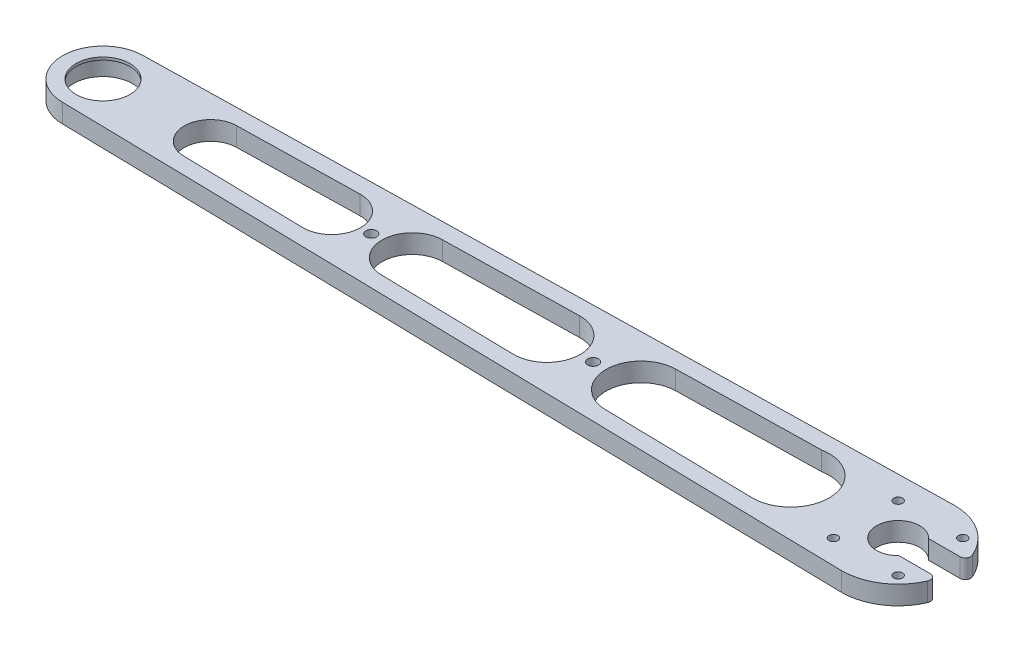
SolidWorks part; units mm, degrees
material "1060 Alloy"
ref_plane "Front Plane" through (0, 0, 0) normal (0, 0, 1) x (1, 0, 0)
ref_plane "Top Plane" through (0, 0, 0) normal (0, 1, 0) x (1, 0, 0)
ref_plane "Right Plane" through (0, 0, 0) normal (1, 0, 0) x (0, 0, -1)
sketch "Sketch1" plane through (0, 0, 0) normal (0, 1, 0) x (1, 0, 0)
  line L0 (-44.2539, 0) -> (44.2539, 0) construction
  line L1 (247.4804, -21) -> (-48.0196, -15)
  line L2 (-48.0196, 15) -> (247.4804, 21)
  line L3 (253.2898, 5.5) -> (264.9375, 5.5)
  line L4 (253.2898, -5.5) -> (264.9375, -5.5)
  arc A0 (-48.0196, 15) -> (-48.0196, -15) centre (-48.0196, 0) ccw
  arc A1 (246.6279, -20.9827) -> (266.775, -8.2895) centre (247.4804, 0) ccw
  arc A2 (253.2898, 5.5) -> (253.2898, -5.5) centre (247.4804, 0) ccw
  arc A3 (266.775, 8.2895) -> (246.6279, 20.9827) centre (247.4804, 0) ccw
  arc A4 (264.9375, 5.5) -> (266.775, 8.2895) centre (264.9375, 7.5) ccw
  arc A5 (264.9375, -5.5) -> (266.775, -8.2895) centre (264.9375, -7.5) cw
  circle A6 centre (-48.0196, 0) radius 10
  point P16 (267.7473, 5.5)
  dimension "D1" = 42
  dimension "D2" = 30
  dimension "D4" = 16
  dimension "D7" = 2
  dimension "D3" = 295.5
  dimension "D5" = 11
  dimension "D6" = 5.5
extrude "Boss-Extrude1" add sketch "Sketch1" along normal blind 7 contours A5 L4 A2 L3 A4 A3 L2 A0 L1 A1 A6 region at (111.8502, 0, 0)
ref_axis "Axis1" through (247.4804, 52.1339, 0) along (0, -1, 0)
ref_plane "Plane1" through (123.7402, 0, 123.7402) normal (0.7071, 0, 0.7071) x (0, -1, 0)
hole_wizard "Tap Drill for M4 Tap1" positions "Sketch2" profile "Sketch3" hole size "M4" standard "ISO"
sketch "Sketch2" plane through (0, 7, 0) normal (0, 1, 0) x (1, 0, 0)
  line L0 (96.347, -151.1333) -> (151.1333, -96.347) construction
  point P0 (259.5012, 12.0208)
  dimension "D1" = 17
sketch "Sketch3" plane through (259.5012, 7, -12.0208) normal (1, 0, 0) x (0, 0, 1)
  line L0 (0, 0) -> (0, 8.9914)
  line L1 (0, 8.9914) -> (1.65, 8)
  line L2 (1.65, 8) -> (1.65, 0)
  line L5 (1.65, 0) -> (0, 0)
  line L10 (0, 8.9914) -> (-1.65, 8) construction
  line L11 (0, -6.35) -> (0, 107.95) construction
  dimension "Hole Dia." = 3.3
  dimension "Hole Depth" = 8
  dimension "Drill Angle" = 118
pattern_circular "CirPattern1" count 4 over 360 about axis through (247.4804, 52.1339, 0) along (0, -1, 0) of "Tap Drill for M4 Tap1"
sketch "Sketch4" plane through (0, 0, 0) normal (0, 1, 0) x (1, 0, 0)
  circle A0 centre (-48.0196, 0) radius 11
extrude "Cut-Extrude2" cut sketch "Sketch4" along normal blind 6
hole_wizard "M4 Tapped Hole1" positions "Sketch5" profile "Sketch6" tap size "M4" standard "ISO"
sketch "Sketch5" plane through (0, 0, 0) normal (0, -1, 0) x (-1, 0, 0)
  line L0 (-44.2539, 0) -> (44.2539, 0) construction
  circle A0 centre (48.0196, 0) radius 11 construction
  point P0 (33.0196, -10)
  point P2 (33.0196, 10)
  dimension "D1" = 15
  dimension "D2" = 0
  dimension "D3" = 10
  dimension "D4" = 10
sketch "Sketch6" plane through (-33.0196, 0, 10) normal (1, 0, 0) x (0, 0, -1)
  line L0 (0, 0) -> (0, 5.9914)
  line L1 (0, 5.9914) -> (1.65, 5)
  line L2 (1.65, 5) -> (1.65, 0)
  line L5 (1.65, 0) -> (0, 0)
  line L10 (0, 5.9914) -> (-1.65, 5) construction
  line L11 (0, -6.35) -> (0, 107.95) construction
  dimension "Tap Drill Dia." = 3.3
  dimension "Tap Drill Depth" = 5
  dimension "Drill Angle" = 118
cosmetic thread "Hole Thread1" parameters "D1"=5, "D2"=4
cosmetic thread "Hole Thread2" parameters "D1"=5, "D2"=4
sketch "Sketch7" plane through (0, 0, 0) normal (0, -1, 0) x (-1, 0, 0)
  line L0 (8.2188, -9.8069) -> (-36.7627, -10.7202)
  line L1 (8.2188, 9.8069) -> (-36.7627, 10.7202)
  line L2 (-247.4804, -21) -> (48.0196, -15) construction
  line L3 (48.0196, 15) -> (-247.4804, 21) construction
  line L4 (-44.2539, 0) -> (44.2539, 0) construction
  line L5 (-66.7503, 11.3291) -> (-116.7297, 12.3439)
  line L6 (-66.7503, -11.3291) -> (-116.7297, -12.3439)
  line L7 (-151.7153, -13.0543) -> (-207.1907, -14.1807)
  line L8 (-151.7153, 13.0543) -> (-204.9183, 14.1346)
  line L9 (-138.9234, 0) -> (-129.3268, 0) construction
  line L10 (-55.6489, 0) -> (-47.7028, 0) construction
  arc A0 (8.2188, -9.8069) -> (8.2188, 9.8069) centre (8.0196, 0) ccw
  arc A1 (-207.1907, -14.1807) -> (-204.9183, 14.1346) centre (-207.4805, 0.0914) cw
  arc A2 (-36.7627, -10.7202) -> (-36.7627, 10.7202) centre (-36.9804, 0) cw
  arc A3 (-66.7503, 11.3291) -> (-66.7503, -11.3291) centre (-66.9804, 0) cw
  circle A4 centre (48.0196, 0) radius 10 construction
  arc A5 (-116.7297, 12.3439) -> (-116.7297, -12.3439) centre (-116.9804, 0) ccw
  arc A6 (-151.7153, 13.0543) -> (-151.7153, -13.0543) centre (-151.9804, 0) cw
  circle A7 centre (-134.1251, 0) radius 2
  circle A8 centre (-51.6759, 0) radius 2
  point P37 (-51.6759, 0)
  point P39 (-134.1251, 0)
  dimension "D9" = 4
  dimension "D1" = 6
  dimension "D2" = 6
  dimension "D4" = 40
  dimension "D3" = 40
  dimension "D5" = 30
  dimension "D6" = 45
  dimension "D7" = 35
  dimension "D8" = 50
extrude "Cut-Extrude3" cut sketch "Sketch7" against normal blind 7
equation "\"wallthickness\"=6"
equation "\"D1@Sketch7\"=\"wallthickness\""
equation "\"D2@Sketch7\"=\"wallthickness\""
